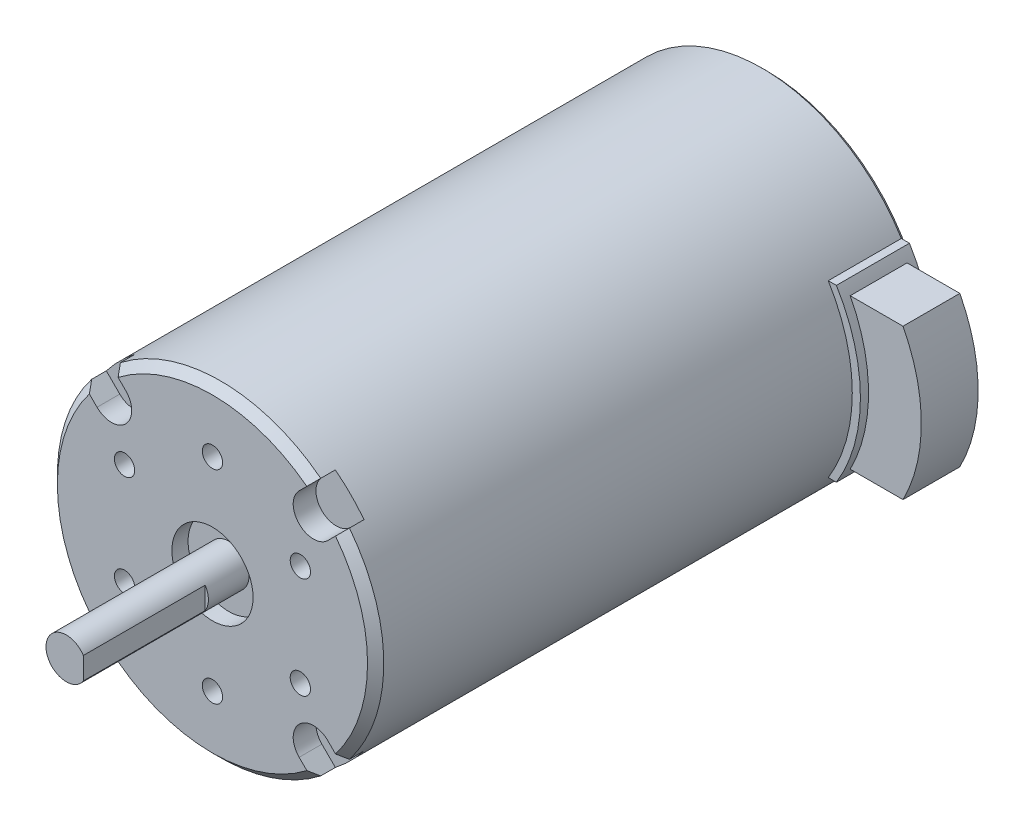
SolidWorks part; units mm, degrees
ref_plane "Спереди" through (0, 0, 0) normal (0, 0, 1) x (1, 0, 0)
ref_plane "Сверху" through (0, 0, 0) normal (0, 1, 0) x (1, 0, 0)
ref_plane "Справа" through (0, 0, 0) normal (1, 0, 0) x (0, 0, -1)
sketch "Эскиз1" plane through (0, 0, 0) normal (0, 0, 1) x (1, 0, 0)
  circle A0 centre (0, 0) radius 20.1
  dimension "D1" = 40.2
extrude "Бобышка-Вытянуть1" add sketch "Эскиз1" along normal blind 68.2
sketch "Эскиз2" plane through (0, 0, 68.2) normal (0, 0, 1) x (1, 0, 0)
  circle A0 centre (0, 0) radius 5
  dimension "D1" = 10
extrude "Вырез-Вытянуть1" cut sketch "Эскиз2" against normal blind 2
sketch "Эскиз3" plane through (0, 0, 66.2) normal (0, 0, 1) x (1, 0, 0)
  circle A0 centre (0, 0) radius 2.5
  dimension "D1" = 5
extrude "Бобышка-Вытянуть2" add sketch "Эскиз3" along normal blind 20
sketch "Эскиз4" plane through (0, 0, 86.2) normal (0, 0, 1) x (1, 0, 0)
  line L0 (-2.5, 7.6597) -> (-2.5, -10.4127) construction
  line L1 (2.1, 7.6597) -> (2.1, -8.8167) construction
  line L2 (2.1, 1.3565) -> (2.1, -1.3565)
  circle A0 centre (0, 0) radius 2.5 construction
  circle A1 centre (0, 0) radius 2.5 construction
  arc A2 (2.1, 1.3565) -> (2.1, -1.3565) centre (0, 0) cw
  dimension "D1" = 4.6
extrude "Вырез-Вытянуть2" cut sketch "Эскиз4" against normal blind 15
chamfer "Фаска1" distance 1 angle 45 1 edges at (20.1, 0, 68.2)
sketch "Эскиз5" plane through (0, 0, 68.2) normal (0, 0, 1) x (1, 0, 0)
  line L0 (0, 19.1) -> (0, -19.1) construction
  line L1 (-16.5411, -9.55) -> (16.5411, 9.55) construction
  line L2 (16.5411, -9.55) -> (-16.5411, 9.55) construction
  circle A0 centre (0, 0) radius 19.1 construction
  circle A1 centre (0, 0) radius 12.5 construction
  dimension "D3" = 25
  dimension "D1" = 60
  dimension "D2" = 60
hole_wizard "Отверстие обработанное метчиком M3x0.51" positions "Эскиз7" profile "Эскиз6" tap size "M3x0.5" standard "Ansi Metric"
sketch "Эскиз7" plane through (0, 0, 68.2) normal (0, 0, 1) x (1, 0, 0)
  line L0 (16.5411, -9.55) -> (-16.5411, 9.55) construction
  line L1 (0, 19.1) -> (0, -19.1) construction
  line L2 (-16.5411, -9.55) -> (16.5411, 9.55) construction
  circle A0 centre (0, 0) radius 12.5 construction
  point P0 (-10.8253, 6.25)
  point P6 (0, 12.5)
  point P10 (10.8253, 6.25)
  point P14 (10.8253, -6.25)
  point P16 (0, -12.5)
  point P18 (-10.8253, -6.25)
sketch "Эскиз6" plane through (-10.8253, 6.25, 68.2) normal (1, 0, 0) x (0, -1, 0)
  line L0 (0, 0) -> (0, 9.2511)
  line L1 (0, 9.2511) -> (1.25, 8.5)
  line L2 (1.25, 8.5) -> (1.25, 0)
  line L5 (1.25, 0) -> (0, 0)
  line L10 (0, 9.2511) -> (-1.25, 8.5) construction
  line L11 (0, -6.35) -> (0, 107.95) construction
  dimension "Диаметр сверла" = 2.5
  dimension "Глубина сверла" = 8.5
  dimension "Угол заточки сверла" = 118
cosmetic thread "Отверстие резьбы1" parameters "D1"=6, "D2"=3
cosmetic thread "Отверстие резьбы2" parameters "D1"=6, "D2"=3
cosmetic thread "Отверстие резьбы3" parameters "D1"=6, "D2"=3
cosmetic thread "Отверстие резьбы4" parameters "D1"=6, "D2"=3
cosmetic thread "Отверстие резьбы5" parameters "D1"=6, "D2"=3
cosmetic thread "Отверстие резьбы6" parameters "D1"=6, "D2"=3
sketch "Эскиз8" plane through (0, 0, 68.2) normal (0, 0, 1) x (1, 0, 0)
  line L0 (13.5057, 13.5057) -> (-13.5057, -13.5057) construction
  line L1 (-13.5057, 13.5057) -> (13.5057, -13.5057) construction
  line L2 (0, 19.1) -> (0, -19.1) construction
  line L3 (-14.2128, 10.6773) -> (-15.8702, 12.3347)
  line L4 (-10.6773, 14.2128) -> (-12.3347, 15.8702)
  line L5 (14.2128, 10.6773) -> (15.8702, 12.3347)
  line L6 (10.6773, 14.2128) -> (12.3347, 15.8702)
  line L7 (10.6773, -14.2128) -> (12.3347, -15.8702)
  line L8 (14.2128, -10.6773) -> (15.8702, -12.3347)
  line L9 (-14.2128, -10.6773) -> (-15.8702, -12.3347)
  line L10 (-10.6773, -14.2128) -> (-12.3347, -15.8702)
  circle A0 centre (0, 0) radius 19.1 construction
  arc A1 (-14.2128, 10.6773) -> (-10.6773, 14.2128) centre (-12.4451, 12.4451) ccw
  circle A2 centre (0, 0) radius 20.1 construction
  arc A3 (-15.8702, 12.3347) -> (-12.3347, 15.8702) centre (0, 0) cw
  arc A4 (10.6773, 14.2128) -> (14.2128, 10.6773) centre (12.4451, 12.4451) ccw
  arc A5 (12.3347, 15.8702) -> (15.8702, 12.3347) centre (0, 0) cw
  arc A6 (14.2128, -10.6773) -> (10.6773, -14.2128) centre (12.4451, -12.4451) ccw
  arc A7 (15.8702, -12.3347) -> (12.3347, -15.8702) centre (0, 0) cw
  arc A8 (-10.6773, -14.2128) -> (-14.2128, -10.6773) centre (-12.4451, -12.4451) ccw
  arc A9 (-12.3347, -15.8702) -> (-15.8702, -12.3347) centre (0, 0) cw
  point P35 (0, 0)
  dimension "D3" = 5
  dimension "D1" = 90
  dimension "D2" = 45
  dimension "D4" = 4
extrude "Вырез-Вытянуть3" cut sketch "Эскиз8" against normal blind 2.8
chamfer "Фаска2" distance 0.5 angle 45 1 edges at (20.1, 0, 0)
ref_plane "Плоскость1" through (30, 0, 0) normal (1, 0, 0) x (0, 0, -1)
sketch "Эскиз9" plane through (30, 0, 0) normal (1, 0, 0) x (0, 0, -1)
  line L0 (0, 0) -> (-68.2, 0) construction
  line L1 (-68.2, 11.6218) -> (-68.2, -11.6218) construction
  line L3 (-9.5, 10.5) -> (-0.5, 10.5)
  line L4 (-9.5, 10.5) -> (-9.5, -10.5)
  line L5 (-9.5, -10.5) -> (-0.5, -10.5)
  line L6 (-0.5, 10.5) -> (-0.5, -10.5)
  line L7 (-9.5, 10.5) -> (-0.5, -10.5) construction
  line L8 (-9.5, -10.5) -> (-0.5, 10.5) construction
  line L9 (-0.5, 20.1) -> (-0.5, -20.1) construction
  point P5 (-5, 0)
  dimension "D1" = 9
  dimension "D2" = 21
extrude "Бобышка-Вытянуть5" add sketch "Эскиз9" along normal blind 1 from surface starting at face at (20.1, 0, 0.5)
sketch "Эскиз10" plane through (30, 0, 0) normal (1, 0, 0) x (0, 0, -1)
  line L1 (-8.5, 9.25) -> (-1.5, 9.25)
  line L2 (-8.5, 9.25) -> (-8.5, -9.25)
  line L3 (-8.5, -9.25) -> (-1.5, -9.25)
  line L4 (-1.5, 9.25) -> (-1.5, -9.25)
  line L5 (-8.5, 9.25) -> (-1.5, -9.25) construction
  line L6 (-8.5, -9.25) -> (-1.5, 9.25) construction
  point P0 (-5, 0)
  dimension "D1" = 7
  dimension "D2" = 18.5
extrude "Бобышка-Вытянуть6" add sketch "Эскиз10" along normal blind 6.5 from surface starting at face at (19.6197, 0, 5)
